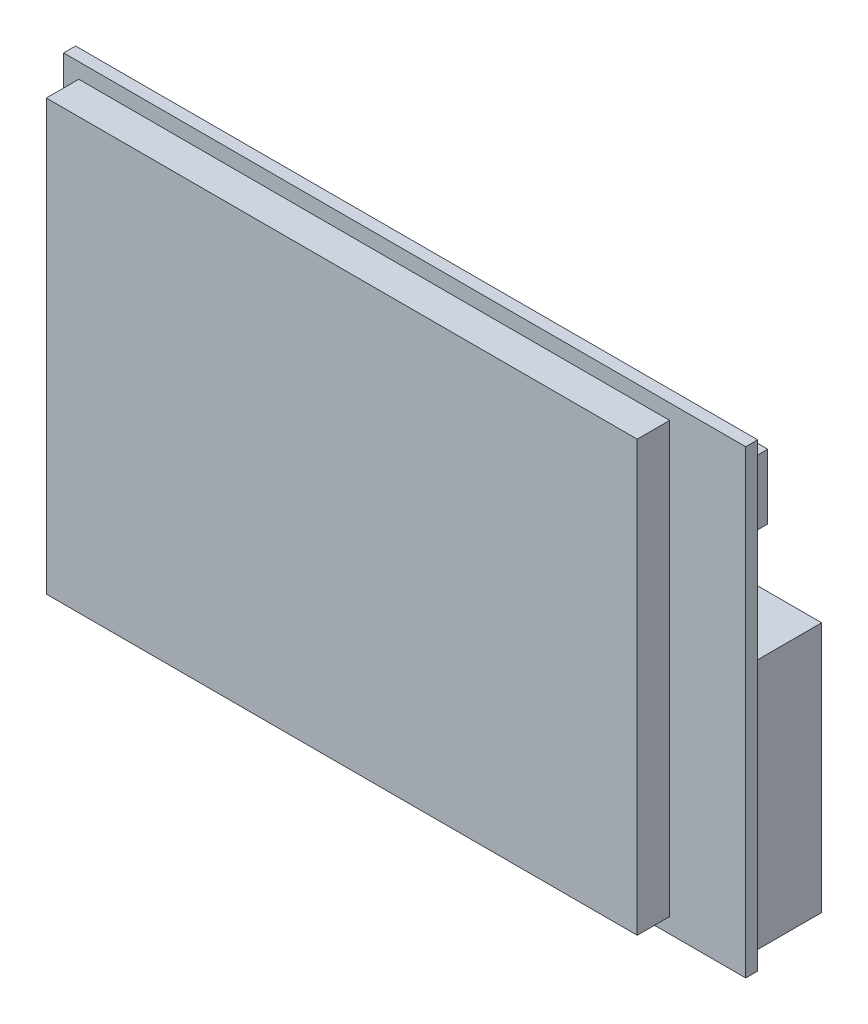
SolidWorks part; units mm, degrees
ref_plane "Front Plane" through (0, 0, 0) normal (0, 0, 1) x (1, 0, 0)
ref_plane "Top Plane" through (0, 0, 0) normal (0, 1, 0) x (1, 0, 0)
ref_plane "Right Plane" through (0, 0, 0) normal (1, 0, 0) x (0, 0, -1)
sketch "Sketch1" plane through (0, 0, 0) normal (0, 0, -1) x (-1, 0, 0)
  line L1 (-32.25, -24.25) -> (32.25, -24.25) construction
  line L2 (-32.25, -24.25) -> (-32.25, 24.25) construction
  line L3 (-32.25, 24.25) -> (32.25, 24.25) construction
  line L4 (32.25, -24.25) -> (32.25, 24.25) construction
  line L5 (-32.25, -24.25) -> (32.25, 24.25) construction
  line L6 (-32.25, 24.25) -> (32.25, -24.25) construction
  line L7 (-36, 28) -> (41.7, 28) construction
  line L8 (-36, 28) -> (-36, -28.5) construction
  line L9 (-36, -28.5) -> (41.7, -28.5) construction
  line L10 (41.7, 28) -> (41.7, -28.5) construction
  line L11 (-46, 30) -> (43.7, 30)
  line L12 (-46, 30) -> (-46, -30.5)
  line L13 (-46, -30.5) -> (43.7, -30.5)
  line L14 (43.7, 30) -> (43.7, -30.5)
  point P0 (0, 0)
  dimension "D1" = 64.5
  dimension "D2" = 48.5
  dimension "D3" = 3.75
  dimension "D4" = 3.75
  dimension "D5" = 56.5
  dimension "D6" = 77.7
  dimension "D7" = 2
  dimension "D8" = 10
  dimension "D9" = 2
  dimension "D10" = 2
extrude "Boss-Extrude1" add sketch "Sketch1" along normal blind 1.5748
sketch "Sketch2" plane through (0, 0, 0) normal (0, 0, -1) x (-1, 0, 0)
  line L1 (-36, -28.5) -> (41.7, -28.5)
  line L2 (-36, -28.5) -> (-36, 28)
  line L3 (-36, 28) -> (41.7, 28)
  line L4 (41.7, -28.5) -> (41.7, 28)
  line L5 (41.7, 28) -> (49.6841, 28) construction
  line L6 (-36, 28) -> (-43.9841, 28) construction
  line L10 (-32.25, -24.25) -> (32.25, -24.25) construction
  line L11 (-32.25, -24.25) -> (-32.25, 24.25) construction
  line L12 (-32.25, 24.25) -> (32.25, 24.25) construction
  line L13 (32.25, -24.25) -> (32.25, 24.25) construction
  line L14 (-32.25, -24.25) -> (32.25, 24.25) construction
  line L15 (-32.25, 24.25) -> (32.25, -24.25) construction
  point P0 (0, 0)
  point P14 (0, 0)
  point P19 (-83.1395, 7.4926)
  dimension "D1" = 56.5
  dimension "D2" = 77.7
  dimension "D3" = 3.75
  dimension "D4" = 48.5
  dimension "D5" = 64.5
  dimension "D6" = 3.75
extrude "Boss-Extrude2" add sketch "Sketch2" against normal blind 4.27
sketch "Sketch3" plane through (0, 0, -1.5748) normal (0, 0, 1) x (1, 0, 0)
  line L1 (45.5416, 4.5) -> (36.5816, 4.5)
  line L2 (45.5416, 4.5) -> (45.5416, -28.5)
  line L3 (45.5416, -28.5) -> (36.5816, -28.5)
  line L4 (36.5816, 4.5) -> (36.5816, -28.5)
  dimension "D1" = 33
  dimension "D2" = 8.96
extrude "Boss-Extrude3" add sketch "Sketch3" against normal blind 8.87
sketch "Sketch4" plane through (0, 0, -1.5748) normal (0, 0, 1) x (1, 0, 0)
  line L1 (38.0878, 25.594) -> (43.3178, 25.594)
  line L2 (38.0878, 25.594) -> (38.0878, 17.064)
  line L3 (38.0878, 17.064) -> (43.3178, 17.064)
  line L4 (43.3178, 25.594) -> (43.3178, 17.064)
  dimension "D1" = 8.53
  dimension "D2" = 5.23
extrude "Boss-Extrude4" add sketch "Sketch4" against normal blind 4
